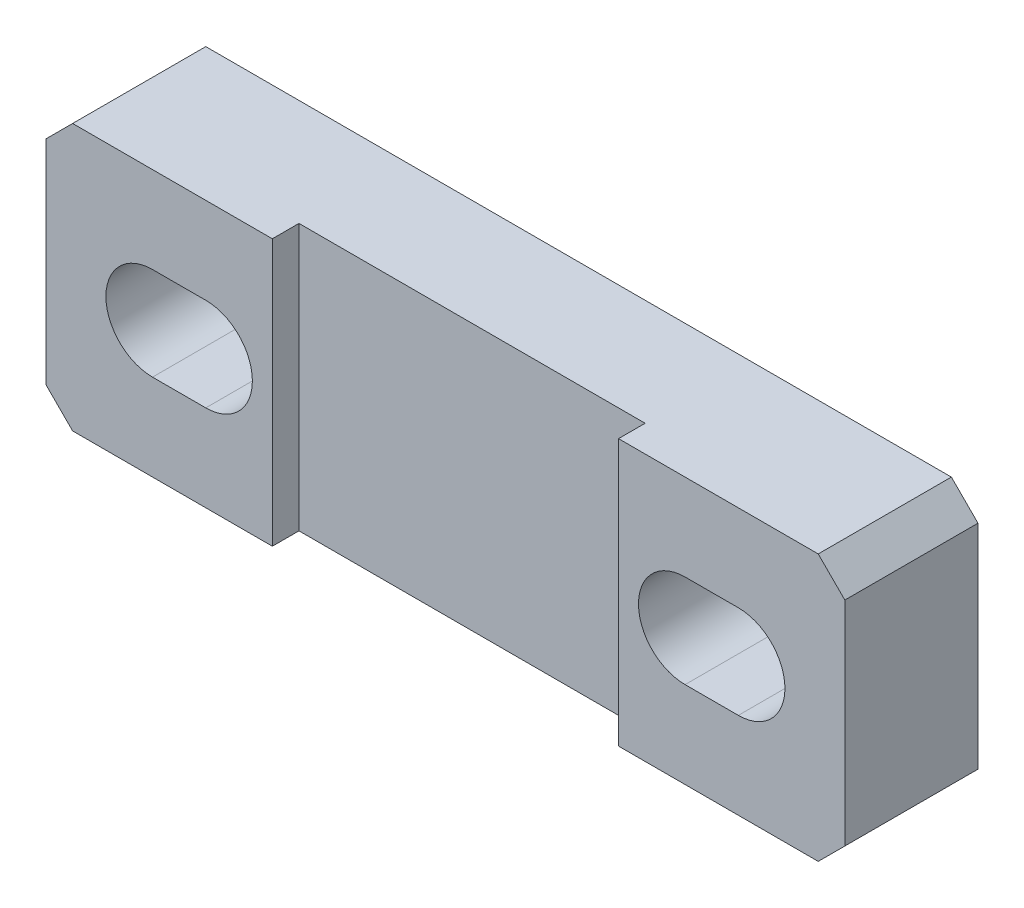
SolidWorks part; units mm, degrees
material "Lega 1060"
ref_plane "Piano frontale" through (0, 0, 0) normal (0, 0, 1) x (1, 0, 0)
ref_plane "Piano superiore" through (0, 0, 0) normal (0, 1, 0) x (1, 0, 0)
ref_plane "Piano destro" through (0, 0, 0) normal (1, 0, 0) x (0, 0, -1)
sketch "Schizzo2" plane through (0, 0, 0) normal (0, 0, 1) x (1, 0, 0)
  line L0 (0, 0) -> (-15, 0) construction
  line L1 (15, -5) -> (-15, -5)
  line L2 (15, -5) -> (15, 5)
  line L3 (15, 5) -> (-15, 5)
  line L4 (-15, -5) -> (-15, 5)
  line L5 (15, -5) -> (-15, 5) construction
  line L6 (15, 5) -> (-15, -5) construction
  line L7 (-9, 0) -> (-11, 0) construction
  line L8 (-9, -1.75) -> (-11, -1.75)
  line L9 (-9, 1.75) -> (-11, 1.75)
  line L10 (0, 0) -> (0, 5) construction
  line L11 (9, 0) -> (11, 0) construction
  line L12 (9, -1.75) -> (11, -1.75)
  line L13 (9, 1.75) -> (11, 1.75)
  arc A0 (-9, -1.75) -> (-9, 1.75) centre (-9, 0) ccw
  arc A1 (-11, 1.75) -> (-11, -1.75) centre (-11, 0) ccw
  arc A2 (9, -1.75) -> (9, 1.75) centre (9, 0) cw
  arc A3 (11, 1.75) -> (11, -1.75) centre (11, 0) cw
  point P0 (0, 0)
  point P10 (-10, 0)
  point P18 (10, 0)
  dimension "D1" = 10
  dimension "D2" = 30
  dimension "D3" = 10
  dimension "D4" = 2
  dimension "D5" = 3.5
extrude "Estrusione-Estrusione1" add sketch "Schizzo2" against normal blind 5
sketch "Schizzo3" plane through (0, 0, 0) normal (0, 0, 1) x (1, 0, 0)
  line L0 (15, 5) -> (-15, 5) construction
  line L1 (6.5, -5) -> (-6.5, -5)
  line L2 (6.5, -5) -> (6.5, 5)
  line L3 (6.5, 5) -> (-6.5, 5)
  line L4 (-6.5, -5) -> (-6.5, 5)
  line L5 (6.5, -5) -> (-6.5, 5) construction
  line L6 (6.5, 5) -> (-6.5, -5) construction
  point P0 (0, 0)
  dimension "D1" = 13
extrude "Taglio-Estrusione1" cut sketch "Schizzo3" against normal blind 1
chamfer "Smusso1" distance 1 angle 45 4 edges at (15, -5, -2.5) (15, 5, -2.5) (-15, -5, -2.5) (-15, 5, -2.5)
